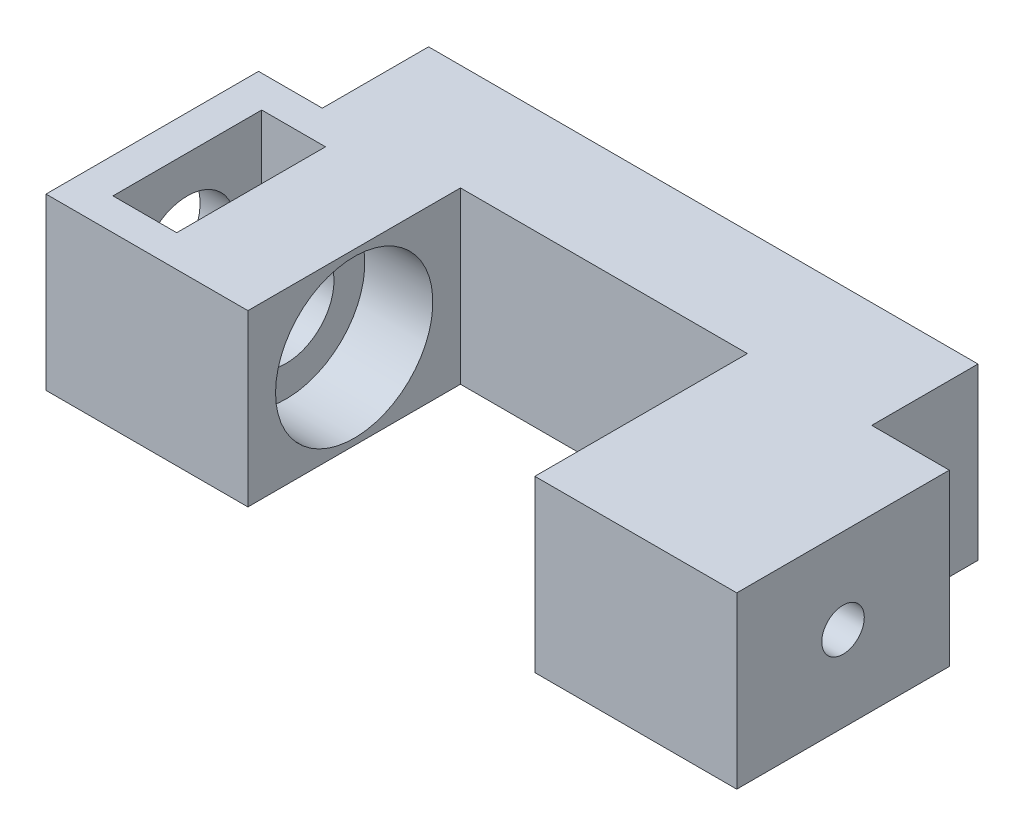
SolidWorks part; units mm, degrees
material "ABS"
ref_plane "Plan de face" through (0, 0, 0) normal (0, 0, 1) x (1, 0, 0)
ref_plane "Plan de dessus" through (0, 0, 0) normal (0, 1, 0) x (1, 0, 0)
ref_plane "Plan de droite" through (0, 0, 0) normal (1, 0, 0) x (0, 0, -1)
sketch "Length" plane through (0, 0, 0) normal (0, 1, 0) x (1, 0, 0)
  line L0 (0, 0) -> (0, 117) construction
  dimension "D1" = 117
sketch "Length2" plane through (0, 0, 0) normal (1, 0, 0) x (0, 0, -1)
  line L0 (100, 0) -> (100, 40) construction
  line L1 (0, 0) -> (117, 0) construction
  dimension "D1" = 40
  dimension "D2" = 100
sketch3d "TopPlane"
sketch "Esquisse17" plane through (0, 40, 0) normal (0, -1, 0) x (-1, 0, 0)
  line L0 (13.25, 105) -> (13.25, 95)
  line L1 (13.25, 95) -> (6.75, 95)
  line L2 (6.75, 95) -> (6.75, 105)
  line L3 (6.75, 105) -> (-6.75, 105)
  line L4 (-6.75, 105) -> (-6.75, 95)
  line L5 (-6.75, 95) -> (-13.25, 95)
  line L6 (-13.25, 95) -> (-13.25, 105)
  line L7 (-13.25, 105) -> (-13.25, 110)
  line L8 (-13.25, 110) -> (13.25, 110)
  line L9 (13.25, 110) -> (13.25, 105)
  line L10 (0, 0) -> (0, 117) construction
  line L11 (0, 100) -> (13.25, 100) construction
  line L12 (13.25, 105) -> (6.75, 105) construction
  line L13 (-6.75, 105) -> (-13.25, 105) construction
  line L14 (-10, 105) -> (-10, 95) construction
  line L15 (10, 105) -> (10, 95) construction
  point P12 (0, 105)
  dimension "D1" = 6.5
  dimension "D2" = 5
  dimension "D3" = 20
  dimension "D4" = 10
  dimension "D5" = 5
extrude "Shape" add sketch "Esquisse17" along normal blind 4 and the other way blind 4 separate body
sketch "Esquisse19" plane through (-13.25, 0, 0) normal (-1, 0, 0) x (0, 0, 1)
  circle A0 centre (-100, 40) radius 2.25
  dimension "D1" = 4.5
extrude "HoleAxe_motor" cut sketch "Esquisse19" against normal blind 13
sketch "Esquisse20" plane through (6.75, 0, 0) normal (-1, 0, 0) x (0, 0, 1)
  circle A0 centre (-100, 40) radius 3.7
  dimension "D1" = 7.4
extrude "HoleBearing_motor" cut sketch "Esquisse20" against normal blind 3.2
mirror "Symétrie3" about plane through (0, 0, 0) normal (1, 0, 0) of "HoleBearing_motor"
sketch "Esquisse21" plane through (9.95, 0, 0) normal (-1, 0, 0) x (0, 0, 1)
  circle A0 centre (-100, 40) radius 2.2
  circle A1 centre (-100, 40) radius 3.7 construction
  dimension "D1" = 1.5
extrude "entretoiseBearing_motor" cut sketch "Esquisse21" against normal blind 1
sketch "Esquisse22" plane through (-13.25, 0, 0) normal (-1, 0, 0) x (0, 0, 1)
  line L0 (-95, 36) -> (-110, 36) construction
  line L1 (-95, 44) -> (-105, 44)
  line L2 (-95, 44) -> (-95, 36)
  line L3 (-95, 36) -> (-105, 36)
  line L4 (-105, 44) -> (-105, 36)
  circle A0 centre (-100, 40) radius 2.25
  circle A1 centre (-100, 40) radius 2.25 construction
extrude "Ext_motor" add sketch "Esquisse22" along normal blind 3
sketch "Esquisse23" plane through (0, 44, 0) normal (0, 1, 0) x (1, 0, 0)
  line L0 (-13.25, 105) -> (-6.75, 105) construction
  line L1 (-9.95, 95) -> (-9.95, 105) construction
  line L2 (-6.75, 95) -> (-16.25, 95) construction
  line L3 (-9.95, 100) -> (-16.25, 100) construction
  line L4 (-16.25, 95) -> (-16.25, 105) construction
  line L5 (-9.95, 96.3) -> (-9.95, 103.7) construction
  line L7 (-14.6, 96.5) -> (-11.6, 96.5)
  line L8 (-14.6, 96.5) -> (-14.6, 103.5)
  line L9 (-14.6, 103.5) -> (-11.6, 103.5)
  line L10 (-11.6, 96.5) -> (-11.6, 103.5)
  line L11 (-14.6, 96.5) -> (-11.6, 103.5) construction
  line L12 (-14.6, 103.5) -> (-11.6, 96.5) construction
  point P14 (-13.1, 100)
  dimension "D1" = 3
  dimension "D2" = 7
extrude "HoleScrewLess_motor" cut sketch "Esquisse23" against normal blind 10
sketch "Esquisse24" plane through (13.25, 0, 0) normal (1, 0, 0) x (0, 0, -1)
  line L5 (105, 44) -> (105, 36) construction
  line L6 (105, 36) -> (95, 36)
  line L7 (105, 36) -> (105, 44)
  line L8 (105, 44) -> (95, 44)
  line L9 (95, 36) -> (95, 44)
  line L10 (105, 36) -> (95, 44) construction
  line L11 (105, 44) -> (95, 36) construction
  point P0 (100, 40)
extrude "Boss.-Extru.1" add sketch "Esquisse24" along normal blind 3
sketch "Esquisse25" plane through (13.25, 0, 0) normal (1, 0, 0) x (0, 0, -1)
  line L1 (105, 36) -> (110, 36)
  line L2 (105, 36) -> (105, 44)
  line L3 (105, 44) -> (110, 44)
  line L4 (110, 36) -> (110, 44)
extrude "Adjustment attach" cut sketch "Esquisse25" against normal blind 0.65
sketch "Esquisse26" plane through (10.95, 0, 0) normal (-1, 0, 0) x (0, 0, 1)
  circle A0 centre (-100, 40) radius 1
  dimension "D1" = 2
extrude "Remove helper" cut sketch "Esquisse26" against normal blind 10
equation "\"entretoiseBearing\"= 1.5mm"
equation "\"length_tibia\"= 206mm"
equation "\"length_femur\"= 117mm"
equation "\"length_coxa\"= 27mm"
equation "\"height\"= 40mm"
equation "\"width\"= 100mm"
equation "\"lever\"= 40mm"
equation "\"depthMagnet\"= 1mm"
equation "\"D1@Length\"=\"length_femur\""
equation "\"D1@Length2\"=\"height\""
equation "\"D1@Esquisse19\"=\"entretoiseBearing\"+3"
equation "\"D1@Esquisse21\"=\"entretoiseBearing\""
equation "\"D2@Length2\"=\"width\""
equation "\"D1@Ref\" = \"length_femur\""
equation "\"errorFlat\"= 0.20mm"
equation "\"errorCircle\"= 0.40mm"
equation "\"cuticule\"=1.5mm"
equation "\"D1@Esquisse20\"=\"errorCircle\"+7"
equation "\"D1@HoleBearing_motor\"=\"errorFlat\"+3"
equation "\"D1@Adjustment attach\"=0.45 + \"errorFlat\""
